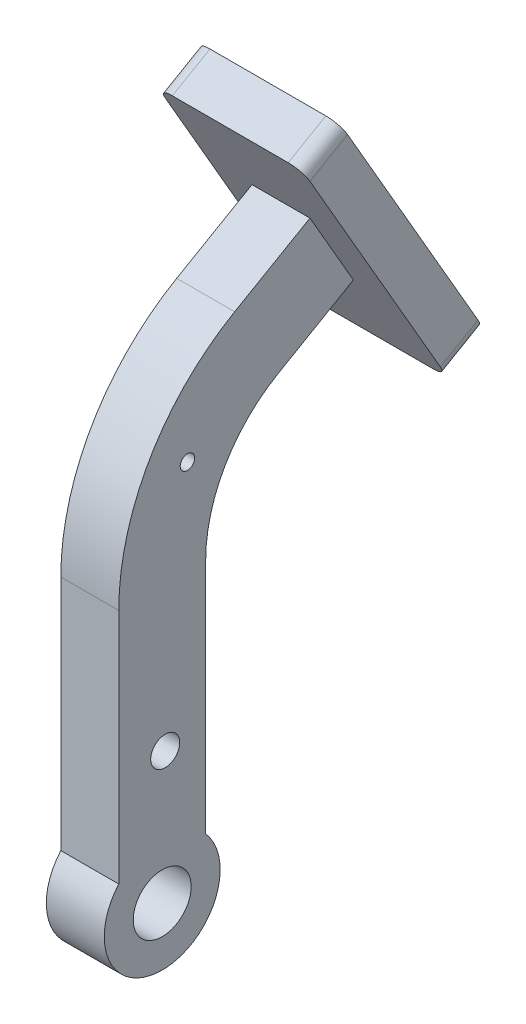
SolidWorks part; units mm, degrees
ref_plane "Front Plane" through (0, 0, 0) normal (0, 0, 1) x (1, 0, 0)
ref_plane "Top Plane" through (0, 0, 0) normal (0, 1, 0) x (1, 0, 0)
ref_plane "Right Plane" through (0, 0, 0) normal (1, 0, 0) x (0, 0, -1)
sketch "Image" plane through (0, 0, 0) normal (1, 0, 0) x (0, 0, -1)
  line L0 (294.3509, 636.9257) -> (533.3607, 636.9257) construction
sketch "Sketch3" plane through (0, 0, 0) normal (1, 0, 0) x (0, 0, -1)
  line L0 (46.4711, 217.0929) -> (96.4711, 130.4904)
  line L1 (96.4711, 130.4904) -> (83.4808, 122.9904)
  line L2 (83.4808, 122.9904) -> (33.4808, 209.5929)
  line L3 (33.4808, 209.5929) -> (46.4711, 217.0929)
  line L4 (50.9808, 179.282) -> (25, 164.282)
  line L5 (40, 138.3013) -> (65.9808, 153.3013)
  line L6 (-15, 95) -> (-15, 13.2288)
  line L7 (25, 164.282) -> (65, 95) construction
  line L8 (15, 13.2288) -> (15, 95)
  line L9 (65, 95) -> (-15, 95) construction
  line L10 (-4.282, 135) -> (21.6987, 120) construction
  arc A0 (25, 164.282) -> (-15, 95) centre (65, 95) ccw
  arc A1 (40, 138.3013) -> (15, 95) centre (65, 95) ccw
  arc A2 (-15, 13.2288) -> (15, 13.2288) centre (0, 0) ccw
  circle A3 centre (0, 0) radius 10
  circle A4 centre (1.0325, 45) radius 5
  circle A6 centre (8.7083, 127.5) radius 2.5
  dimension "D3" = 80
  dimension "D4" = 50
  dimension "D14" = 40
  dimension "D15" = 20
  dimension "D12" = 10
  dimension "D13" = 5
  dimension "D1" = 15
  dimension "D2" = 100
  dimension "D5" = 95
  dimension "D6" = 30
  dimension "D7" = 30
  dimension "D8" = 60
  dimension "D9" = 30
  dimension "D10" = 35
  dimension "D11" = 50
extrude "Boss-Extrude1" add sketch "Sketch3" along normal mid plane 20 contours L6 A2 L8 A1 L5 L2 L4 A0 A4 A3 region at (0, 86.2265, -10.1176)
extrude "Boss-Extrude2" add sketch "Sketch3<3>" along normal mid plane 50 contours L3 L2 L1 L0 region at (0, 170.0417, -64.976)
sketch "Sketch3<3>" plane through (0, 0, 0) normal (1, 0, 0) x (0, 0, -1) same geometry as "Sketch3"
fillet "Fillet1" radius 5 4 edges at (25, 213.3429, -39.976) (-25, 213.3429, -39.976) (-25, 126.7404, -89.976) (25, 126.7404, -89.976)
sketch "Sketch5" plane through (0, 74.3958, -128.8573) normal (0, 0.5, -0.866) x (-1, 0, 0)
  line L0 (0, 164.7724) -> (0, 64.7724) construction
  line L1 (-20, 164.7724) -> (20, 164.7724) construction
  line L2 (-20, 64.7724) -> (20, 64.7724) construction
  line L3 (-10, 144.7724) -> (10, 144.7724) construction
  line L4 (-10, 149.7724) -> (10, 149.7724)
  line L5 (-10, 139.7724) -> (10, 139.7724)
  line L6 (-10, 114.7724) -> (10, 114.7724) construction
  line L7 (-10, 119.7724) -> (10, 119.7724)
  line L8 (-10, 109.7724) -> (10, 109.7724)
  line L9 (-10, 84.7724) -> (10, 84.7724) construction
  line L10 (-10, 89.7724) -> (10, 89.7724)
  line L11 (-10, 79.7724) -> (10, 79.7724)
  line L12 (-25, 159.7724) -> (-25, 69.7724) construction
  arc A0 (-10, 149.7724) -> (-10, 139.7724) centre (-10, 144.7724) ccw
  arc A1 (10, 139.7724) -> (10, 149.7724) centre (10, 144.7724) ccw
  arc A2 (-10, 119.7724) -> (-10, 109.7724) centre (-10, 114.7724) ccw
  arc A3 (10, 109.7724) -> (10, 119.7724) centre (10, 114.7724) ccw
  arc A4 (-10, 89.7724) -> (-10, 79.7724) centre (-10, 84.7724) ccw
  arc A5 (10, 79.7724) -> (10, 89.7724) centre (10, 84.7724) ccw
  point P8 (0, 144.7724)
  point P14 (0, 114.7724)
  point P22 (0, 84.7724)
  point P29 (-15, 144.7724)
  dimension "D2" = 5
  dimension "D1" = 20
  dimension "D3" = 20
  dimension "D4" = 20
  dimension "D5" = 15
  dimension "D6" = 10
extrude "Boss-Extrude3" add sketch "Sketch5" along normal blind 2
fillet "Fillet5" radius 1 12 edges at (15, 174.7917, -73.2032) (0, 179.1218, -70.7032) (-15, 174.7917, -73.2032) (15, 200.7724, -58.2032) (0, 205.1025, -55.7032) (-15, 200.7724, -58.2032) (0, 153.141, -85.7032) (-15, 148.8109, -88.2032) (0, 144.4808, -90.7032) (15, 148.8109, -88.2032) (0, 170.4615, -75.7032) (0, 196.4423, -60.7032)
